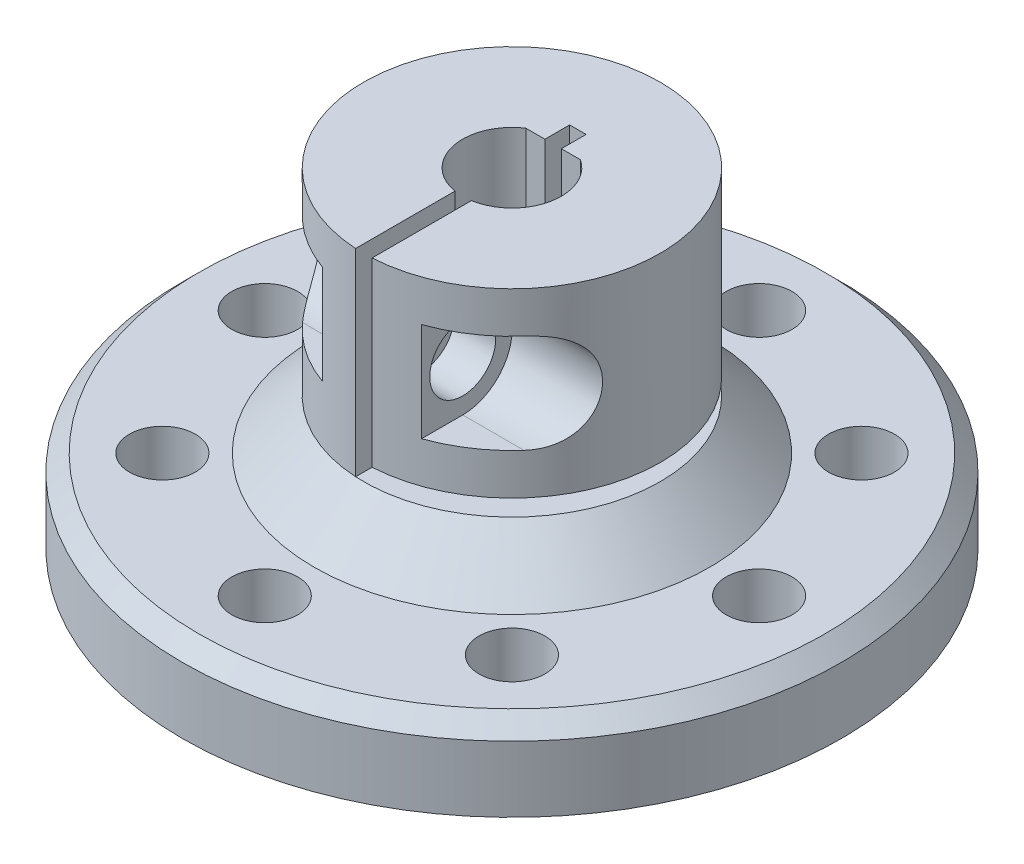
SolidWorks part; units mm, degrees
ref_plane "Front" through (0, 0, 0) normal (0, 0, 1) x (1, 0, 0)
ref_plane "Top" through (0, 0, 0) normal (0, 1, 0) x (1, 0, 0)
ref_plane "Right" through (0, 0, 0) normal (1, 0, 0) x (0, 0, -1)
sketch "Sketch1" plane through (0, 0, 0) normal (0, 1, 0) x (1, 0, 0)
  circle A0 centre (0, 0) radius 20
  dimension "D1" = 40
extrude "Boss-Extrude1" add sketch "Sketch1" along normal blind 5
sketch "Sketch2" plane through (0, 5, 0) normal (0, 1, 0) x (1, 0, 0)
  circle A0 centre (0, 15) radius 2
  circle A1 centre (10.6066, 10.6066) radius 2
  circle A2 centre (15, 0) radius 2
  circle A3 centre (10.6066, -10.6066) radius 2
  circle A4 centre (0, -15) radius 2
  circle A5 centre (-10.6066, -10.6066) radius 2
  circle A6 centre (-15, 0) radius 2
  circle A7 centre (-10.6066, 10.6066) radius 2
  point P4 (0, 0)
  point P19 (0, 0)
  point P20 (0, 0)
  point P21 (-18.4603, 0)
  dimension "D1" = 4
  dimension "D2" = 15
  dimension "D3" = 8
extrude "Cut-Extrude1" cut sketch "Sketch2" against normal through all
sketch "Sketch3" plane through (0, 5, 0) normal (0, 1, 0) x (1, 0, 0)
  circle A0 centre (0, 0) radius 9
  dimension "D1" = 18
extrude "Boss-Extrude2" add sketch "Sketch3" along normal blind 15
sketch "Sketch4" plane through (0, 20, 0) normal (0, 1, 0) x (1, 0, 0)
  line L0 (-1.6583, 2.5) -> (1.6583, 2.5)
  line L1 (0, 0) -> (0, -3) construction
  circle A0 centre (0, 0) radius 3
  dimension "D1" = 6
  dimension "D2" = 5.5
extrude "Cut-Extrude2" cut sketch "Sketch4" against normal through all contours L0 A0 region at (0, 20, 0.112)
sketch "Sketch5" plane through (0, 20, 0) normal (0, 1, 0) x (1, 0, 0)
  line L1 (-0.5, -9) -> (0.5, -9)
  line L2 (-0.5, -9) -> (-0.5, 4)
  line L3 (-0.5, 4) -> (0.5, 4)
  line L4 (0.5, -9) -> (0.5, 4)
  line L5 (-0.5, -9) -> (0.5, 4) construction
  line L6 (-0.5, 4) -> (0.5, -9) construction
  circle A0 centre (0, 0) radius 9 construction
  point P0 (0, -2.5)
  point P5 (0, 0)
  dimension "D1" = 1
  dimension "D2" = 4
extrude "Cut-Extrude3" cut sketch "Sketch5" against normal blind 12
ref_plane "Plane1" through (9, 0, 0) normal (1, 0, 0) x (0, 0, -1)
sketch "Sketch7" plane through (9, 0, 0) normal (1, 0, 0) x (0, 0, -1)
  line L0 (9, 5) -> (9, 20) construction
  line L1 (9, 8) -> (-8.9861, 8)
  line L2 (9, 8) -> (9, 9)
  line L3 (9, 9) -> (-8.9861, 9)
  line L4 (-8.9861, 8) -> (-8.9861, 9)
  line L5 (-8.9861, 20) -> (-8.9861, 8) construction
  line L6 (-8.9861, 8) -> (-9, 8) construction
  dimension "D1" = 1
extrude "Cut-Extrude4" cut sketch "Sketch7" against normal up to surface (9.5 mm away) up to face at (-0.5, 14, 5.9721)
sketch "Sketch8" plane through (9, 0, 0) normal (1, 0, 0) x (0, 0, -1)
  line L0 (-8.9861, 20) -> (-8.9861, 9) construction
  line L1 (-5.9861, 17.5) -> (-8.9861, 17.5)
  line L2 (-8.9861, 17.5) -> (-8.9861, 11.5)
  line L3 (-8.9861, 11.5) -> (-5.9861, 11.5)
  line L4 (9, 9) -> (9, 20) construction
  line L5 (9, 14.5) -> (-17.854, 14.5) construction
  circle A0 centre (-5.9861, 14.5) radius 3
  point P14 (-6.4861, 16.5)
  point P15 (-6.052, 16.5)
  dimension "D1" = 6
extrude "Cut-Extrude5" cut sketch "Sketch8" against normal blind 6 contours A0 | A0 L1 L2 | A0 L2 L3 region at (9, 16.8299, 8.316) region at (9, 14.5, 5.9861) region at (9, 12.1701, 8.316)
mirror "Mirror1" about plane through (0, 0, 0) normal (1, 0, 0) of "Cut-Extrude5"
sketch "Sketch9" plane through (3, 0, 0) normal (1, 0, 0) x (0, 0, -1)
  circle A0 centre (-5.9861, 14.5) radius 2
  arc A1 (-5.9861, 11.5) -> (-5.9861, 17.5) centre (-5.9861, 14.5) ccw construction
  dimension "D1" = 4
extrude "Cut-Extrude6" cut sketch "Sketch9" against normal through all
chamfer "Chamfer3" distance 3 distance2 3 1 edges at (0, 5, 9)
chamfer "Chamfer4" distance 1 angle 45 1 edges at (0, 5, 20)
